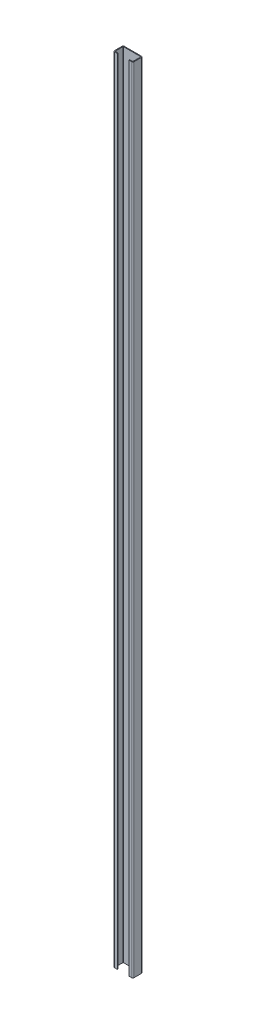
SolidWorks part; units mm, degrees
note: The reader was unsure of these and kept them because the rebuilt part matched: thickness of "Base-Flange1", "Edge-Flange1", "Edge-Flange2", "Sheet-Metal1", "Sheet-Metal2", "Sheet-Metal3", "Sheet-Metal4"; flange length of "Edge-Flange1", "Edge-Flange2".
ref_plane "Front Plane" through (0, 0, 0) normal (0, 0, 1) x (1, 0, 0)
ref_plane "Top Plane" through (0, 0, 0) normal (0, 1, 0) x (1, 0, 0)
ref_plane "Right Plane" through (0, 0, 0) normal (1, 0, 0) x (0, 0, -1)
sketch "BaseFlange" plane through (0, 0, 0) normal (0, 0, 1) x (1, 0, 0)
  line L1 (25, 1025) -> (-25, 1025)
  line L2 (25, 1025) -> (25, -1025)
  line L3 (25, -1025) -> (-25, -1025)
  line L4 (-25, 1025) -> (-25, -1025)
  line L5 (25, 1025) -> (-25, -1025) construction
  line L6 (25, -1025) -> (-25, 1025) construction
  point P0 (0, 0)
  dimension "D1" = 50
  dimension "Height" = 2050
base flange "Base-Flange1" sketch "BaseFlange" thickness 2 reverse thickness direction yes parameters "D1"=1
edge flange "Edge-Flange1" sketch "Sketch10" flange profiles "Sketch10", "Sketch11" flange angle 90 flange length 25 flange position material inside bend radius 1 thickness 2 relief rectangular parameters "D6"=10, "D8"=1
sketch "Sketch10" plane through (25, 0, 2) normal (-1, 0, 0) x (0, -1, 0)
  line L1 (-1025, 0) -> (1025, 0) construction
  line L2 (1025, 0) -> (1025, 23)
  line L3 (1025, 23) -> (-1025, 23)
  line L4 (-1025, 23) -> (-1025, 0)
  line L5 (-1025, 0) -> (1025, 0)
sketch "Sketch11" plane through (-25, 0, 2) normal (1, 0, 0) x (0, 1, 0)
  line L0 (-1025, 0) -> (1025, 0) construction
  line L1 (-1025, 0) -> (1025, 0)
  line L2 (-1025, 0) -> (-1025, 23)
  line L3 (-1025, 23) -> (1025, 23)
  line L4 (1025, 23) -> (1025, 0)
bend "EdgeBend1" bend radius 1 bend angle 90 parameters "D5"=1
bend "EdgeBend2" bend radius 1 bend angle 90 parameters "D5"=2
edge flange "Edge-Flange2" sketch "Sketch16" flange profiles "Sketch16", "Sketch17" flange angle 90 flange length 10 flange position material inside bend radius 1 thickness 2 relief rectangular parameters "D6"=10, "D8"=1
sketch "Sketch16" plane through (-23, 0, 25) normal (0, 0, 1) x (0, -1, 0)
  line L2 (1025, 0) -> (1025, 8)
  line L3 (1025, 8) -> (-1025, 8)
  line L4 (-1025, 8) -> (-1025, 0)
  line L5 (1025, 0) -> (-1025, 0) construction
  line L6 (1025, 0) -> (-1025, 0)
sketch "Sketch17" plane through (23, 0, 25) normal (0, 0, 1) x (0, 1, 0)
  line L0 (1025, 0) -> (-1025, 0) construction
  line L1 (1025, 0) -> (-1025, 0)
  line L2 (1025, 0) -> (1025, 8)
  line L3 (1025, 8) -> (-1025, 8)
  line L4 (-1025, 8) -> (-1025, 0)
bend "EdgeBend3" bend radius 1 bend angle 90 parameters "D5"=3
bend "EdgeBend4" bend radius 1 bend angle 90 parameters "D5"=4
sketch "Sketch18" plane through (0, 0, 0) normal (0, 0, 1) x (1, 0, 0)
  line L0 (22, 1025) -> (-22, 1025) construction
  line L1 (-22, -1025) -> (22, -1025) construction
  line L2 (0, 17.5) -> (0, -17.5) construction
  circle A0 centre (0, -17.5) radius 1.6
  circle A1 centre (0, -942.5) radius 1.6
  circle A2 centre (0, 942.5) radius 1.6
  circle A3 centre (0, -907.5) radius 1.6
  circle A4 centre (0, 17.5) radius 1.6
  circle A5 centre (0, 907.5) radius 1.6
  dimension "D3" = 3.2
  dimension "D4" = 35
  dimension "D5" = 35
  dimension "D6" = 35
  dimension "D1" = 82.5
  dimension "D2" = 82.5
extrude "Cut-Extrude1" cut sketch "Sketch18" along normal through all normal cut yes
sketch "Bend-Lines1" [suppressed] plane through (0, 0, 0) normal (0, 1, 0) x (1, 0, 0)
sketch "Bounding-Box1" [suppressed] plane through (0, 0, 0) normal (0, 1, 0) x (1, 0, 0)
sheet metal parameters "Sheet-Metal1" thickness 2 parameters "D1"=1
flat pattern "Flat-Pattern1" [suppressed]
sketch "Bend-Lines2" plane through (0, 0, 0) normal (0, 1, 0) x (1, 0, 0)
sketch3d "Bounding-Box2" [suppressed]
  line L0 (-40, 950, 0) -> (-40, -950, 0) construction
  line L1 (40, 950, 0) -> (40, -950, 0) construction
  line L2 (-40, 950, 0) -> (40, 950, 0) construction
  line L3 (-40, -950, 0) -> (40, -950, 0) construction
sheet metal parameters "Sheet-Metal2" thickness 2 parameters "D1"=1
flat pattern "Flat-Pattern1"
sketch "Bend-Lines2" plane through (0, 0, 0) normal (0, 0, 1) x (1, 0, 0)
  line L0 (-23.2017, 947.5) -> (-23.2017, -947.5) construction
  line L1 (23.2017, -947.5) -> (23.2017, 947.5) construction
  line L2 (-23.2017, 947.5) -> (-23.2017, -947.5) construction
  line L3 (23.2017, -947.5) -> (23.2017, 947.5) construction
sketch3d "Bounding-Box2" [suppressed]
  line L0 (46.4033, 947.5, 0) -> (46.4033, -947.5, 0) construction
  line L1 (-46.4033, 947.5, 0) -> (-46.4033, -947.5, 0) construction
  line L2 (46.4033, 947.5, 0) -> (-46.4033, 947.5, 0) construction
  line L3 (46.4033, -947.5, 0) -> (-46.4033, -947.5, 0) construction
bend of the flat pattern "Flatten-<EdgeBend1>1"
bend of the flat pattern "Flatten-<EdgeBend2>1"
sheet metal parameters "Sheet-Metal3" thickness 2 parameters "D1"=1
flat pattern "Flat-Pattern1"
sketch "Bend-Lines2" plane through (0, 0, 0) normal (0, 0, 1) x (1, 0, 0)
  line L0 (-23.2017, 1025) -> (-23.2017, -1025) construction
  line L1 (23.2017, -1025) -> (23.2017, 1025) construction
  line L2 (-23.2017, 1025) -> (-23.2017, -1025) construction
  line L3 (23.2017, -1025) -> (23.2017, 1025) construction
  line L4 (44.605, -1025) -> (44.605, 1025) construction
  line L5 (-44.605, 1025) -> (-44.605, -1025) construction
  line L6 (44.605, -1025) -> (44.605, 1025) construction
  line L7 (-44.605, 1025) -> (-44.605, -1025) construction
sketch3d "Bounding-Box2" [suppressed]
  line L0 (52.8066, 1025, 0) -> (52.8066, -1025, 0) construction
  line L1 (-52.8066, 1025, 0) -> (-52.8066, -1025, 0) construction
  line L2 (52.8066, 1025, 0) -> (-52.8066, 1025, 0) construction
  line L3 (52.8066, -1025, 0) -> (-52.8066, -1025, 0) construction
bend of the flat pattern "Flatten-<EdgeBend1>1"
bend of the flat pattern "Flatten-<EdgeBend2>1"
bend of the flat pattern "Flatten-<EdgeBend3>1"
bend of the flat pattern "Flatten-<EdgeBend4>1"
sheet metal parameters "Sheet-Metal4" thickness 2 parameters "D1"=1
flat pattern "Flat-Pattern1"
sketch "Bend-Lines2" plane through (0, 0, 0) normal (0, 0, -1) x (-1, 0, 0)
  line L0 (23.2017, -1025) -> (23.2017, 1025) construction
  line L1 (-23.2017, 1025) -> (-23.2017, -1025) construction
  line L2 (23.2017, -1025) -> (23.2017, 1025) construction
  line L3 (-23.2017, 1025) -> (-23.2017, -1025) construction
  line L4 (-44.605, 1025) -> (-44.605, -1025) construction
  line L5 (44.605, -1025) -> (44.605, 1025) construction
  line L6 (-44.605, 1025) -> (-44.605, -1025) construction
  line L7 (44.605, -1025) -> (44.605, 1025) construction
sketch3d "Bounding-Box2" [suppressed]
  line L0 (-52.8066, 1025, 0) -> (-52.8066, -1025, 0) construction
  line L1 (52.8066, 1025, 0) -> (52.8066, -1025, 0) construction
  line L2 (-52.8066, 1025, 0) -> (52.8066, 1025, 0) construction
  line L3 (-52.8066, -1025, 0) -> (52.8066, -1025, 0) construction
bend of the flat pattern "Flatten-<EdgeBend1>1"
bend of the flat pattern "Flatten-<EdgeBend2>1"
bend of the flat pattern "Flatten-<EdgeBend3>1"
bend of the flat pattern "Flatten-<EdgeBend4>1"
